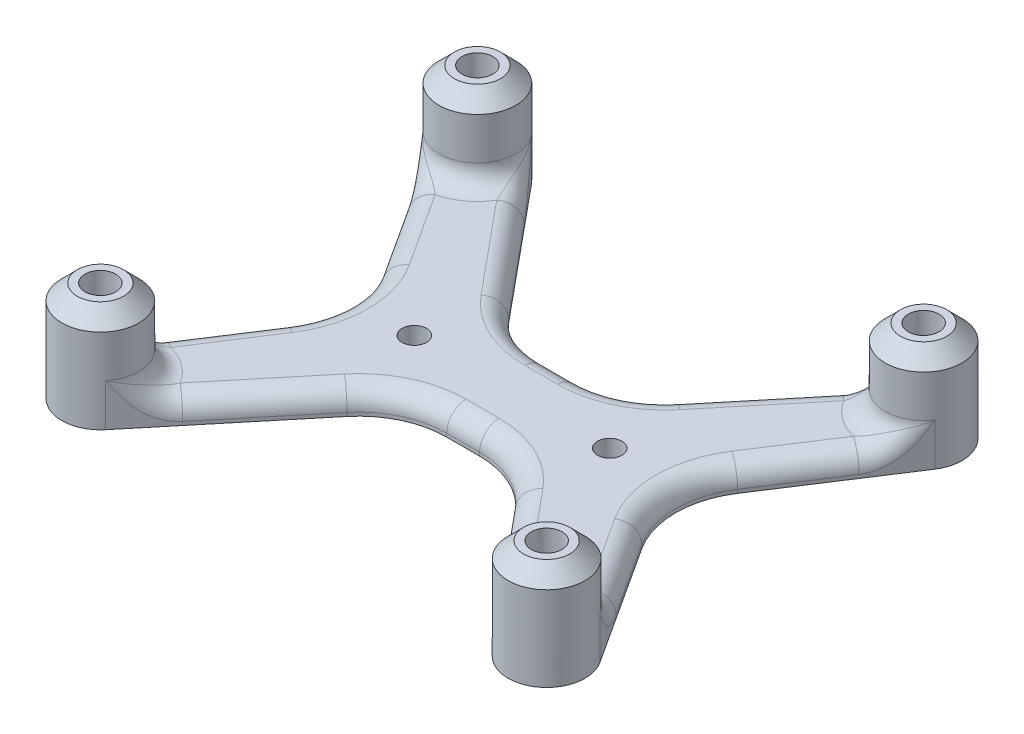
SolidWorks part; units mm, degrees
ref_plane "Front Plane" through (0, 0, 0) normal (0, 0, 1) x (1, 0, 0)
ref_plane "Top Plane" through (0, 0, 0) normal (0, 1, 0) x (1, 0, 0)
ref_plane "Right Plane" through (0, 0, 0) normal (1, 0, 0) x (0, 0, -1)
sketch "Sketch1" plane through (0, 0, 0) normal (0, 1, 0) x (1, 0, 0)
  line L0 (-7.5163, 6.35) -> (7.5163, 6.35)
  line L1 (-29, -24.5) -> (29, -24.5) construction
  line L2 (-29, -24.5) -> (-29, 24.5) construction
  line L3 (-29, 24.5) -> (29, 24.5) construction
  line L4 (29, -24.5) -> (29, 24.5) construction
  line L5 (-29, -24.5) -> (29, 24.5) construction
  line L6 (-29, 24.5) -> (29, -24.5) construction
  line L7 (-19.05, -6.35) -> (19.05, -6.35) construction
  line L8 (-19.05, -6.35) -> (-19.05, 6.35) construction
  line L9 (-19.05, 6.35) -> (19.05, 6.35) construction
  line L10 (19.05, -6.35) -> (19.05, 6.35) construction
  line L11 (-19.05, -6.35) -> (19.05, 6.35) construction
  line L12 (-19.05, 6.35) -> (19.05, -6.35) construction
  line L13 (7.5163, 6.35) -> (25.1456, 27.6849)
  line L14 (19.05, 0) -> (33.1932, 21.7766)
  line L15 (19.05, 0) -> (33.1932, -21.7766)
  line L16 (25.1456, -27.6849) -> (7.5163, -6.35)
  line L17 (7.5163, -6.35) -> (-7.5163, -6.35)
  line L18 (-7.5163, -6.35) -> (-25.1456, -27.6849)
  line L19 (-19.05, 0) -> (-33.1932, -21.7766)
  line L20 (-19.05, 0) -> (-33.1932, 21.7766)
  line L21 (-25.1456, 27.6849) -> (-7.5163, 6.35)
  circle A0 centre (-29, -24.5) radius 5
  circle A1 centre (29, -24.5) radius 5
  circle A2 centre (29, 24.5) radius 5
  circle A3 centre (-29, 24.5) radius 5
  point P0 (0, 0)
  point P6 (0, 0)
  dimension "D5" = 10
  dimension "D6" = 10
  dimension "D7" = 10
  dimension "D8" = 10
  dimension "D1" = 12.7
  dimension "D2" = 38.1
  dimension "D3" = 58
  dimension "D4" = 49
extrude "Boss-Extrude1" add sketch "Sketch1" along normal blind 3 contours A0 | A3 L20 L19 A0 L18 L17 L16 A1 L15 L14 A2 L13 L0 L21 | A3 | A2 | A1 region at (0, 0, 0) region at (-29, 0, -24.5) region at (29, 0, -24.5) region at (-29, 0, 24.5) region at (29, 0, 24.5)
sketch "Sketch2" plane through (0, 3, 0) normal (0, 1, 0) x (1, 0, 0)
  circle A0 centre (-29, -24.5) radius 5
  circle A1 centre (29, -24.5) radius 5
  circle A2 centre (29, 24.5) radius 5
  circle A3 centre (-29, 24.5) radius 5
extrude "Boss-Extrude2" add sketch "Sketch2" along normal blind 10
sketch "Sketch3" plane through (0, 13, 0) normal (0, 1, 0) x (1, 0, 0)
  circle A0 centre (-29, -24.5) radius 2
  circle A1 centre (-29, 24.5) radius 2
  circle A2 centre (29, 24.5) radius 2
  circle A3 centre (29, -24.5) radius 2
  dimension "D1" = 4
  dimension "D2" = 4
  dimension "D3" = 4
  dimension "D4" = 4
extrude "Cut-Extrude1" cut sketch "Sketch3" against normal blind 4.8
fillet "Fillet2" radius 11.43 4 edges at (7.5163, 1.5, -6.35) (-7.5163, 1.5, -6.35) (7.5163, 1.5, 6.35) (-7.5163, 1.5, 6.35)
fillet "Fillet3" radius 11.43 2 edges at (-19.05, 1.5, 0) (19.05, 1.5, 0)
fillet "Fillet4" radius 2.54 4 edges at (-26.041, 3, 20.4696) (26.041, 3, 20.4696) (26.041, 3, -20.4696) (-26.041, 3, -20.4696)
fillet "Fillet5" radius 2.54 24 edges at (31.0686, 3.3005, 18.5052) (26.6063, 3, 11.6346) (31.0686, 3.3005, -18.5052) (26.6063, 3, -11.6346) (-22.6609, 3.3005, 24.6779) (-16.2478, 3, 16.9168) (-7.0034, 3, 7.4392) (0, 3, 6.35) (22.6609, 3.3005, 24.6779) (16.2478, 3, 16.9168) (-31.0686, 3.3005, -18.5052) (-26.6063, 3, -11.6346) (-31.0686, 3.3005, 18.5052) (-26.6063, 3, 11.6346) (-22.6609, 3.3005, -24.6779) (-16.2478, 3, -16.9168) (-7.0034, 3, -7.4392) (0, 3, -6.35) (7.0034, 3, -7.4392) (22.6609, 3.3005, -24.6779) (21.2491, 3, 0) (7.0034, 3, 7.4392) (-21.2491, 3, 0) (16.2478, 3, -16.9168)
sketch "Sketch4" plane through (0, 3, 0) normal (0, 1, 0) x (1, 0, 0)
  circle A0 centre (-12.7, 0) radius 1.5875
  circle A1 centre (12.7, 0) radius 1.5875
  dimension "D1" = 3.175
  dimension "D3" = 3.175
  dimension "D2" = 12.7
  dimension "D4" = 12.7
extrude "Cut-Extrude2" cut sketch "Sketch4" against normal through all
chamfer "Chamfer1" distance 2 angle 45 4 edges at (-29, 13, 29.5) (-29, 13, -19.5) (29, 13, -19.5) (29, 13, 29.5)
sketch "Sketch5" plane through (0, 8.2, 0) normal (0, 1, 0) x (1, 0, 0)
  circle A0 centre (-29, -24.5) radius 1.6
  dimension "D1" = 3.2
extrude "Cut-Extrude3" cut sketch "Sketch5" against normal through all
mirror "Mirror1" about plane through (0, 0, 0) normal (1, 0, 0) of "Cut-Extrude3" second plane through (0, 0, 0) second plane normal (0, 0, 1)
